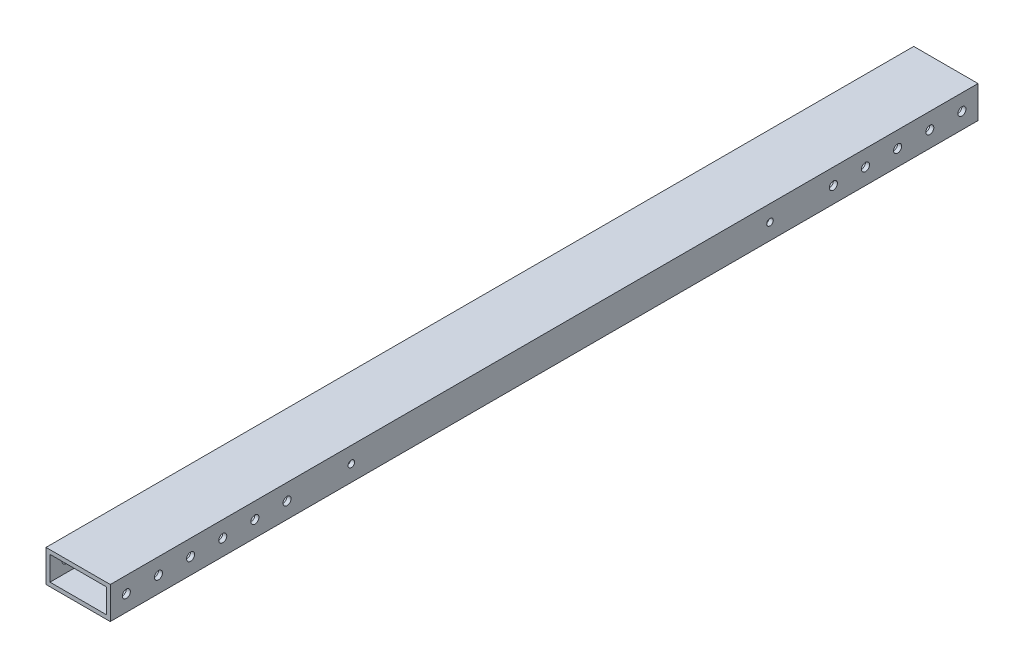
SolidWorks part; units mm, degrees
material "6061 Alloy"
ref_plane "Front Plane" through (0, 0, 0) normal (0, 0, 1) x (1, 0, 0)
ref_plane "Top Plane" through (0, 0, 0) normal (0, 1, 0) x (1, 0, 0)
ref_plane "Right Plane" through (0, 0, 0) normal (1, 0, 0) x (0, 0, -1)
sketch "Sketch1" plane through (0, 0, 0) normal (0, 0, 1) x (1, 0, 0)
  line L0 (-22.225, 9.525) -> (22.225, 9.525)
  line L2 (-25.4, 12.7) -> (25.4, 12.7)
  line L3 (-25.4, 12.7) -> (-25.4, -12.7)
  line L4 (-25.4, -12.7) -> (25.4, -12.7)
  line L5 (25.4, 12.7) -> (25.4, -12.7)
  line L10 (22.225, 9.525) -> (22.225, -9.525)
  line L11 (-22.225, -9.525) -> (22.225, -9.525)
  line L12 (-22.225, 9.525) -> (-22.225, -9.525)
  point P12 (0, 12.7)
  point P14 (25.4, 0)
  dimension "Wall Thickness" = 3.175
  dimension "Outside Width" = 50.8
  dimension "Outside Height" = 25.4
  dimension "Inside Height" = 19.05
  dimension "Inside Width" = 44.45
sketch "Sketch2" plane through (0, 0, 0) normal (1, 0, 0) x (0, 0, -1)
  line L0 (342.9, 0) -> (-342.9, 0)
  point P4 (0, 0)
  point P7 (-342.9, 0)
  point P10 (342.9, 0)
  dimension "Length" = 685.8
sketch "Sketch3" plane through (0, 0, 0) normal (0, 0, 1) x (1, 0, 0)
  line L21 (25.4, 12.7) -> (-25.4, 12.7)
  line L22 (25.4, -12.7) -> (25.4, 12.7)
  line L23 (-25.4, -12.7) -> (25.4, -12.7)
  line L24 (-25.4, 12.7) -> (-25.4, -12.7)
  line L25 (25.4, 12.7) -> (-25.4, 12.7)
  line L26 (25.4, -12.7) -> (25.4, 12.7)
  line L27 (-25.4, -12.7) -> (25.4, -12.7)
  line L28 (-25.4, 12.7) -> (-25.4, -12.7)
  line L29 (22.225, 9.525) -> (-22.225, 9.525)
  line L30 (22.225, -9.525) -> (22.225, 9.525)
  line L31 (-22.225, -9.525) -> (22.225, -9.525)
  line L32 (-22.225, 9.525) -> (-22.225, -9.525)
  line L33 (22.225, 9.525) -> (-22.225, 9.525)
  line L34 (22.225, -9.525) -> (22.225, 9.525)
  line L35 (-22.225, -9.525) -> (22.225, -9.525)
  line L36 (-22.225, 9.525) -> (-22.225, -9.525)
  dimension "D1" = 0
  dimension "D2" = 0
extrude "Boss-Extrude1" add sketch "Sketch3" along normal up to vertex (342.9 mm away) and the other way up to vertex (342.9 mm away) up to point (0, 0, 342.9) other way up to point (0, 0, -342.9)
sketch "Drawing Reference" plane through (0, 0, 0) normal (1, 0, 0) x (0, 0, -1)
  line L0 (-342.9, 0) -> (342.9, 0) construction
  line L1 (0, -12.7) -> (0, 12.7) construction
  line L2 (-342.9, -12.7) -> (342.9, -12.7) construction
  line L5 (-342.9, 12.7) -> (342.9, 12.7) construction
  point P7 (-306.324, 0)
  point P8 (306.324, 0)
  dimension "D1" = 36.576
sketch "Sketch5" plane through (25.4, 0, 0) normal (1, 0, 0) x (0, 0, -1)
  line L0 (-342.9, 0) -> (-279.4, 0)
  line L1 (-342.9, -12.7) -> (-342.9, 12.7) construction
  line L2 (-279.4, 0) -> (-254, 0)
  line L3 (-254, 0) -> (-228.6, 0)
  line L4 (-228.6, 0) -> (-203.2, 0)
sketch "Sketch8" plane through (25.4, 0, 0) normal (1, 0, 0) x (0, 0, -1)
  line L0 (342.9, 0) -> (304.8, 0)
  line L1 (342.9, -12.7) -> (342.9, 12.7) construction
  line L2 (304.8, 0) -> (279.4, 0)
  line L3 (279.4, 0) -> (254, 0)
  line L4 (254, 0) -> (228.6, 0)
  line L5 (342.9, 0) -> (330.2, 0)
hole_wizard "1/4 (0.25) Diameter Hole3" positions "Sketch12" profile "Sketch13" hole size "1/4" standard "ANSI Inch" end condition through all
sketch "Sketch12" plane through (-25.4, 0, 0) normal (-1, 0, 0) x (0, 0, 1)
  point P4 (-330.2, 0)
sketch "Sketch13" plane through (-25.4, 0, -330.2) normal (0, 1, 0) x (0, 0, 1)
  line L0 (0, 0) -> (0, 50.8)
  line L1 (0, 50.8) -> (3.175, 50.8)
  line L2 (3.175, 50.8) -> (3.175, 0)
  line L5 (3.175, 0) -> (0, 0)
  line L11 (0, -6.35) -> (0, 107.95) construction
  dimension "Thru Hole Dia." = 6.35
  dimension "Thru Hole Depth" = 50.8
hole_wizard "1/4 (0.25) Diameter Hole4" positions "Sketch14" profile "Sketch15" hole size "1/4" standard "ANSI Inch" end condition through all
sketch "Sketch14" plane through (-25.4, 0, 0) normal (-1, 0, 0) x (0, 0, 1)
  point P0 (304.8, 0)
  point P3 (330.2, 0)
sketch "Sketch15" plane through (-25.4, 0, 304.8) normal (0, 1, 0) x (0, 0, 1)
  line L0 (0, 0) -> (0, 50.8)
  line L1 (0, 50.8) -> (3.175, 50.8)
  line L2 (3.175, 50.8) -> (3.175, 0)
  line L5 (3.175, 0) -> (0, 0)
  line L11 (0, -6.35) -> (0, 107.95) construction
  dimension "Thru Hole Dia." = 6.35
  dimension "Thru Hole Depth" = 50.8
hole_wizard "1/4 (0.25) Diameter Hole5" positions "Sketch17" profile "Sketch18" hole size "1/4" standard "ANSI Inch" end condition through all
sketch "Sketch17" plane through (25.4, 0, 0) normal (1, 0, 0) x (0, 0, -1)
  point P0 (304.8, 0)
  point P3 (279.4, 0)
sketch "Sketch18" plane through (25.4, 0, -304.8) normal (0, 1, 0) x (0, 0, -1)
  line L0 (0, 0) -> (0, 50.8)
  line L1 (0, 50.8) -> (3.175, 50.8)
  line L2 (3.175, 50.8) -> (3.175, 0)
  line L5 (3.175, 0) -> (0, 0)
  line L11 (0, -6.35) -> (0, 107.95) construction
  dimension "Thru Hole Dia." = 6.35
  dimension "Thru Hole Depth" = 50.8
hole_wizard "1/4 (0.25) Diameter Hole6" positions "Sketch19" profile "Sketch20" hole size "1/4" standard "ANSI Inch" end condition through all
sketch "Sketch19" plane through (25.4, 0, 0) normal (1, 0, 0) x (0, 0, -1)
  point P0 (228.6, 0)
  point P3 (254, 0)
sketch "Sketch20" plane through (25.4, 0, -228.6) normal (0, 1, 0) x (0, 0, -1)
  line L0 (0, 0) -> (0, 50.8)
  line L1 (0, 50.8) -> (3.175, 50.8)
  line L2 (3.175, 50.8) -> (3.175, 0)
  line L5 (3.175, 0) -> (0, 0)
  line L11 (0, -6.35) -> (0, 107.95) construction
  dimension "Thru Hole Dia." = 6.35
  dimension "Thru Hole Depth" = 50.8
hole_wizard "1/4 (0.25) Diameter Hole7" positions "Sketch21" profile "Sketch22" hole size "1/4" standard "ANSI Inch" end condition through all
sketch "Sketch21" plane through (25.4, 0, 0) normal (1, 0, 0) x (0, 0, -1)
  point P0 (-203.2, 0)
  point P3 (-228.6, 0)
sketch "Sketch22" plane through (25.4, 0, 203.2) normal (0, 1, 0) x (0, 0, -1)
  line L0 (0, 0) -> (0, 50.8)
  line L1 (0, 50.8) -> (3.175, 50.8)
  line L2 (3.175, 50.8) -> (3.175, 0)
  line L5 (3.175, 0) -> (0, 0)
  line L11 (0, -6.35) -> (0, 107.95) construction
  dimension "Thru Hole Dia." = 6.35
  dimension "Thru Hole Depth" = 50.8
hole_wizard "1/4 (0.25) Diameter Hole8" positions "Sketch23" profile "Sketch24" hole size "1/4" standard "ANSI Inch" end condition through all
sketch "Sketch23" plane through (25.4, 0, 0) normal (1, 0, 0) x (0, 0, -1)
  point P0 (-279.4, 0)
  point P3 (-254, 0)
sketch "Sketch24" plane through (25.4, 0, 279.4) normal (0, 1, 0) x (0, 0, -1)
  line L0 (0, 0) -> (0, 50.8)
  line L1 (0, 50.8) -> (3.175, 50.8)
  line L2 (3.175, 50.8) -> (3.175, 0)
  line L5 (3.175, 0) -> (0, 0)
  line L11 (0, -6.35) -> (0, 107.95) construction
  dimension "Thru Hole Dia." = 6.35
  dimension "Thru Hole Depth" = 50.8
sketch "Sketch25" plane through (25.4, 0, 0) normal (1, 0, 0) x (0, 0, -1)
  line L0 (-203.2, 0) -> (-152.4, 0)
  line L1 (228.6, 0) -> (178.5118, 0)
hole_wizard "13/64 (0.20313) Diameter Hole1" positions "Sketch26" profile "Sketch27" hole size "13/64" standard "ANSI Inch" end condition through all
sketch "Sketch26" plane through (25.4, 0, 0) normal (1, 0, 0) x (0, 0, -1)
  point P0 (-152.4, 0)
  point P3 (178.5118, 0)
sketch "Sketch27" plane through (25.4, 0, 152.4) normal (0, 1, 0) x (0, 0, -1)
  line L0 (0, 0) -> (0, 50.8)
  line L1 (0, 50.8) -> (2.5798, 50.8)
  line L2 (2.5798, 50.8) -> (2.5798, 0)
  line L5 (2.5798, 0) -> (0, 0)
  line L11 (0, -6.35) -> (0, 107.95) construction
  dimension "Thru Hole Dia." = 5.1595
  dimension "Thru Hole Depth" = 50.8
sketch "Sketch28" plane through (-25.4, 0, 0) normal (-1, 0, 0) x (0, 0, 1)
  line L0 (102.8316, 0) -> (77.4316, 0)
  line L1 (-103.5434, 0) -> (-128.9434, 0)
hole_wizard "1/2 (0.5) Diameter Hole1" positions "Sketch29" profile "Sketch30" hole size "1/2" standard "ANSI Inch"
sketch "Sketch29" plane through (-25.4, 0, 0) normal (-1, 0, 0) x (0, 0, 1)
  point P1 (-591.3016, -480.8022)
  point P3 (-103.5434, 0)
  point P6 (77.4316, 0)
  point P9 (102.8316, 0)
  point P13 (-128.9434, 0)
sketch "Sketch30" plane through (-25.4, -480.8022, -591.3016) normal (0, 1, 0) x (0, 0, 1)
  line L0 (0, 0) -> (0, 10.1655)
  line L1 (0, 10.1655) -> (6.35, 6.35)
  line L2 (6.35, 6.35) -> (6.35, 0)
  line L5 (6.35, 0) -> (0, 0)
  line L10 (0, 10.1655) -> (-6.35, 6.35) construction
  line L11 (0, -6.35) -> (0, 107.95) construction
  dimension "Hole Dia." = 12.7
  dimension "Hole Depth" = 6.35
  dimension "Drill Angle" = 118
equation "\"D1@Drawing Reference\"=\"Outside Width@Sketch1\" * 0.72"
